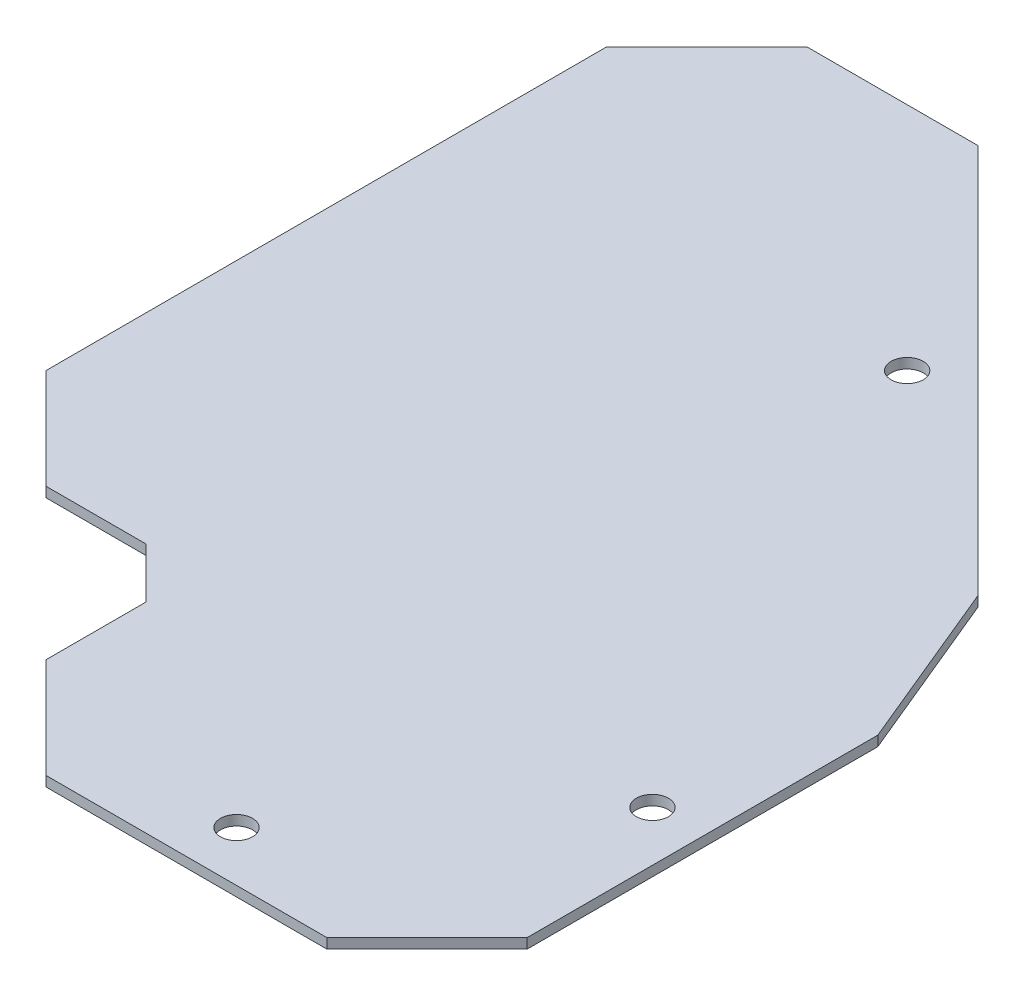
SolidWorks part; units mm, degrees
ref_plane "前视基准面" through (0, 0, 0) normal (0, 0, 1) x (1, 0, 0)
ref_plane "上视基准面" through (0, 0, 0) normal (0, 1, 0) x (1, 0, 0)
ref_plane "右视基准面" through (0, 0, 0) normal (1, 0, 0) x (0, 0, -1)
other "Configuration Table"
sketch "草图1" plane through (0, 0, 0) normal (0, 1, 0) x (1, 0, 0)
  line L0 (0, 0) -> (53.033, 0)
  line L1 (53.033, 0) -> (53.033, 55)
  line L2 (53.033, 55) -> (0, 108.033)
  line L3 (0, 108.033) -> (0, 0)
  dimension "D1" = 45
  dimension "D2" = 75
  dimension "D3" = 55
extrude "凸台-拉伸1" add sketch "草图1" along normal blind 1
sketch "草图2" plane through (0, 0, 0) normal (0, -1, 0) x (1, 0, 0)
  line L0 (0, -30) -> (5, -30)
  line L1 (0, -108.033) -> (0, 0) construction
  line L2 (5, -30) -> (5, 0)
  line L3 (0, 0) -> (53.033, 0) construction
  line L8 (0, -30) -> (0, 0)
  line L9 (0, 0) -> (5, 0)
  dimension "D1" = 30
  dimension "D2" = 5
extrude "切除-拉伸1" cut sketch "草图2" against normal blind 10
chamfer "倒角1" distance 10 angle 45 4 edges at (0, 0.5, -108.033) (5, 0.5, 0) (5, 0.5, -30) (53.033, 0.5, 0)
chamfer "倒角2" distance 10 1 edges at (53.033, 0.5, -55)
sketch "草图3" plane through (0, 0, 0) normal (0, -1, 0) x (1, 0, 0)
  line L0 (22.981, -77.981) -> (26.5165, -81.5165) construction
  line L1 (45.9619, -62.0711) -> (7.0711, -100.9619) construction
  line L2 (48.033, -27.5) -> (53.033, -27.5) construction
  line L3 (53.033, -10) -> (53.033, -45) construction
  line L4 (29.0165, -5) -> (29.0165, 0) construction
  line L5 (15, 0) -> (43.033, 0) construction
  circle A0 centre (22.981, -77.981) radius 1.6
  circle A1 centre (48.033, -27.5) radius 1.6
  circle A2 centre (29.0165, -5) radius 1.6
  dimension "D1" = 5
  dimension "D2" = 3.2
  dimension "D3" = 3.2
  dimension "D6" = 3.2
  dimension "D4" = 5
  dimension "D5" = 5
extrude "切除-拉伸2" cut sketch "草图3" against normal blind 10
sketch "草图4" plane through (0, 0, 0) normal (0, -1, 0) x (1, 0, 0)
  line L1 (0, -100.9619) -> (-20, -100.9619)
  line L2 (0, -100.9619) -> (0, -25)
  line L3 (0, -25) -> (-20, -25)
  line L4 (-20, -100.9619) -> (-20, -25)
  dimension "D1" = 20
extrude "凸台-拉伸2" add sketch "草图4" against normal up to surface (1 mm away) up to face at (22.981, 1, -76.381)
chamfer "倒角3" distance 10 angle 45 2 edges at (-20, 0.5, -25) (-20, 0.5, -100.9619)
